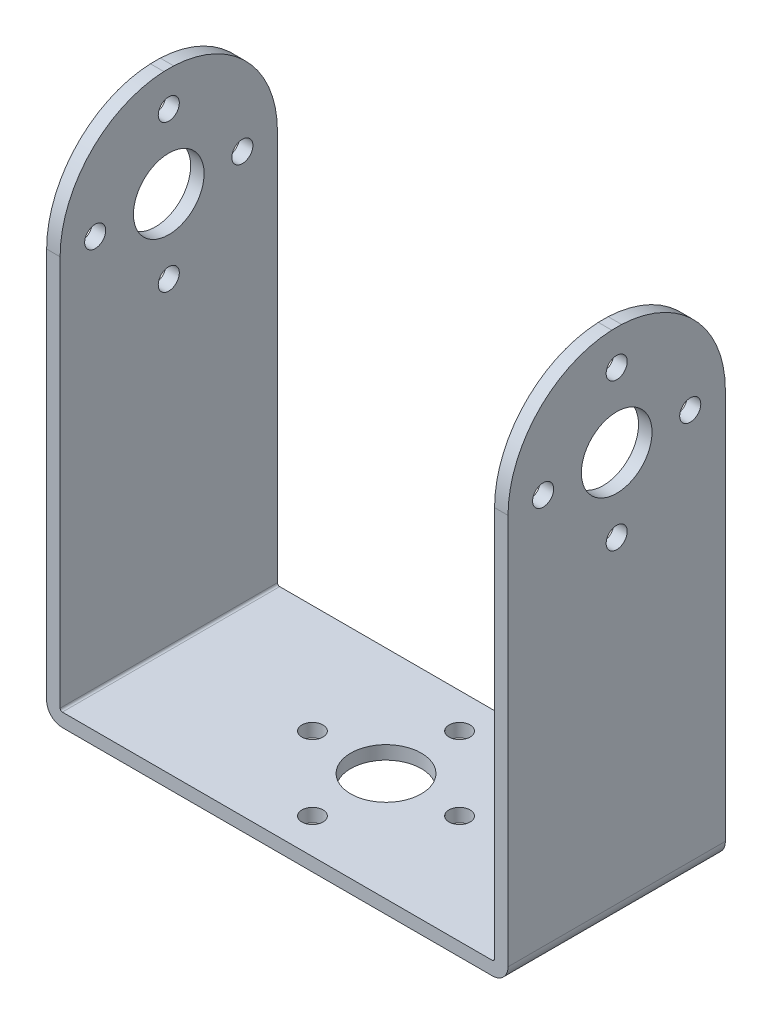
SolidWorks part; units mm, degrees
note: The reader was unsure of these and kept them because the rebuilt part matched: shared geometry of "Sketch1<3>".
ref_plane "Front" through (0, 0, 0) normal (0, 0, 1) x (1, 0, 0)
ref_plane "Top" through (0, 0, 0) normal (0, 1, 0) x (1, 0, 0)
ref_plane "Right" through (0, 0, 0) normal (1, 0, 0) x (0, 0, -1)
sketch "Sketch1" plane through (0, 0, 0) normal (0, 1, 0) x (1, 0, 0)
  line L0 (26.1239, 12.3063) -> (26.1239, -12.3063)
  line L9 (26.1239, -12.3063) -> (-26.1239, -12.3063)
  line L10 (-26.1239, 12.3063) -> (26.1239, 12.3063)
  line L11 (-26.1239, -12.3063) -> (-26.1051, -12.1887)
  line L12 (26.1239, -12.3063) -> (26.1051, -12.1887)
  line L13 (-24.5999, -12.3063) -> (-24.5999, 12.3063)
  line L14 (-26.1239, 12.3063) -> (-26.1239, -12.3063)
  line L15 (24.5999, -12.3063) -> (24.5999, 12.3063)
  circle A5 centre (0, 8.3312) radius 1.1938
  circle A6 centre (-8.3312, 0) radius 1.1938
  circle A7 centre (0, 0) radius 4.0005
  circle A8 centre (8.3312, 0) radius 1.1938
  circle A9 centre (0, -8.3312) radius 1.1938
  point P43 (0, 12.3063)
extrude "Extrude1" add sketch "Sketch1" along normal blind 1.524 contours L9 L15 L10 L13 A9 A5 A6 A7 A8
extrude "Extrude2" add sketch "Sketch1<3>" along normal blind 58.3438
sketch "Sketch1<3>" plane through (0, 0, 0) normal (0, 1, 0) x (1, 0, 0) same geometry as "Sketch1"
sketch "Sketch4" plane through (0, 0, 0) normal (1, 0, 0) x (0, 0, -1)
  line L0 (-12.3063, 58.3438) -> (-12.3063, 46.0502)
  line L1 (-12.3063, 58.3438) -> (12.3063, 58.3438)
  line L2 (12.3063, 58.3438) -> (12.3063, 46.0502)
  line L3 (0, 0) -> (0, 46.0502)
  arc A0 (12.3063, 46.0502) -> (-12.3063, 46.0502) centre (0, 46.0502) ccw
  circle A1 centre (0, 46.0629) radius 4.0005
  circle A3 centre (0, 54.3941) radius 1.1938
  circle A4 centre (8.3312, 46.0629) radius 1.1938
  circle A5 centre (-8.3312, 46.0629) radius 1.1938
  circle A6 centre (0, 37.7317) radius 1.1938
extrude "Cut-Extrude1" cut sketch "Sketch4" against normal blind 40.8686 and the other way blind 40.8686 contours L0 A0 L1 | L1 A0 L2 | A1 | A4 | A3 | A5 | A6
fillet "Fillet1" radius 0.254 2 edges
fillet "Fillet2" radius 1.778 2 edges at (-26.1239, 0, 0) (26.1239, 0, 0)
